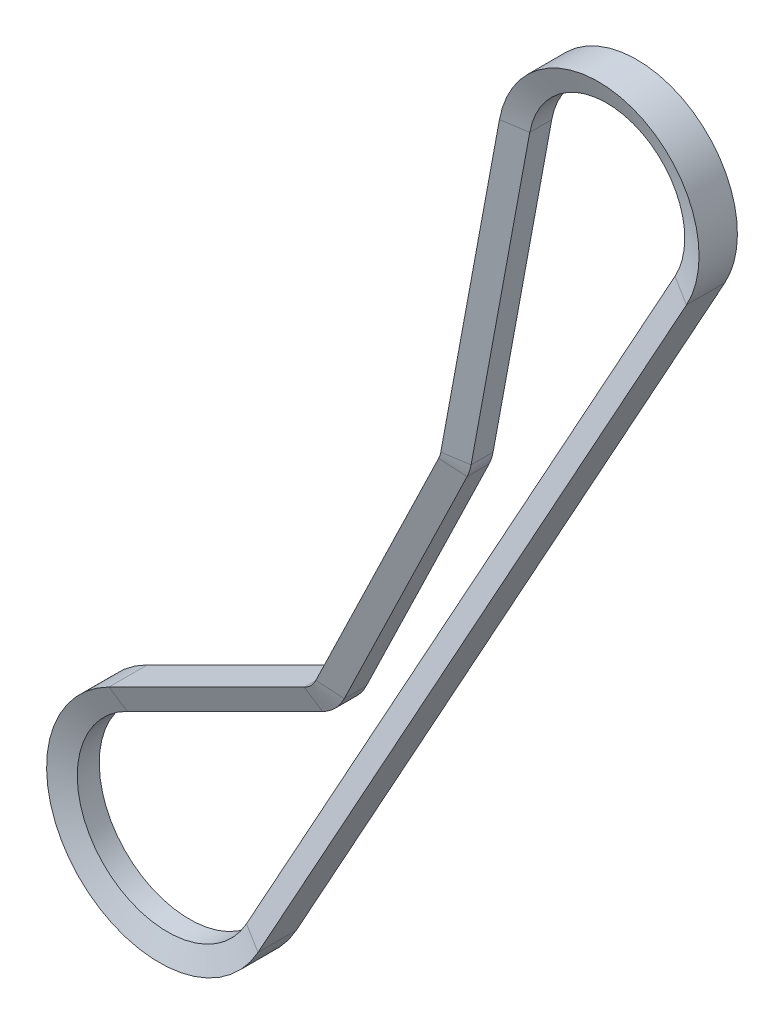
SolidWorks part; units mm, degrees
ref_plane "Front Plane" through (0, 0, 0) normal (0, 0, 1) x (1, 0, 0)
ref_plane "Top Plane" through (0, 0, 0) normal (0, 1, 0) x (1, 0, 0)
ref_plane "Right Plane" through (0, 0, 0) normal (1, 0, 0) x (0, 0, -1)
sketch "Sketch2" plane through (0, 0, 0) normal (0, 0, 1) x (1, 0, 0)
  line L0 (0, 0) -> (1, 0) construction
  line L1 (0, 0) -> (0, 1) construction
  line L12 (21.8783, -12.097) -> (-84.5656, -204.6086)
  line L14 (-121.5716, -166.0061) -> (-73.062, -141.7989)
  line L15 (-70.1819, -138.8841) -> (-39.6795, -75.8793)
  line L16 (-39.1507, -74.2664) -> (-24.5836, 4.544)
  arc A4 (-84.5656, -204.6086) -> (-121.5716, -166.0061) centre (-109.0693, -191.0599) cw
  arc A7 (-24.5836, 4.544) -> (21.8783, -12.097) centre (0, 0) cw
  arc A8 (-73.062, -141.7989) -> (-70.1819, -138.8841) centre (-75.8973, -136.1171) ccw
  arc A9 (-39.6795, -75.8793) -> (-39.1507, -74.2664) centre (-45.3949, -73.1123) ccw
ref_plane "Plane4" through (-24.5836, 4.544, 0) normal (0.1818, 0.9833, 0) x (0.9833, -0.1818, 0)
sketch "Sketch3" plane through (-24.5836, 4.544, 0) normal (0.1818, 0.9833, 0) x (0.9833, -0.1818, 0)
  line L0 (0, -4.7625) -> (0, 4.7625)
  line L1 (0, -4.7625) -> (5.588, -2.7286)
  line L2 (5.588, -2.7286) -> (5.588, 2.7286)
  line L3 (5.588, 2.7286) -> (0, 4.7625)
  line L4 (0, 0) -> (5.588, 0) construction
  dimension "D1" = 9.525
  dimension "D2" = 5.588
  dimension "D3" = 40
sweep "Sweep1" add profiles "Sketch3" path "Sketch2"
